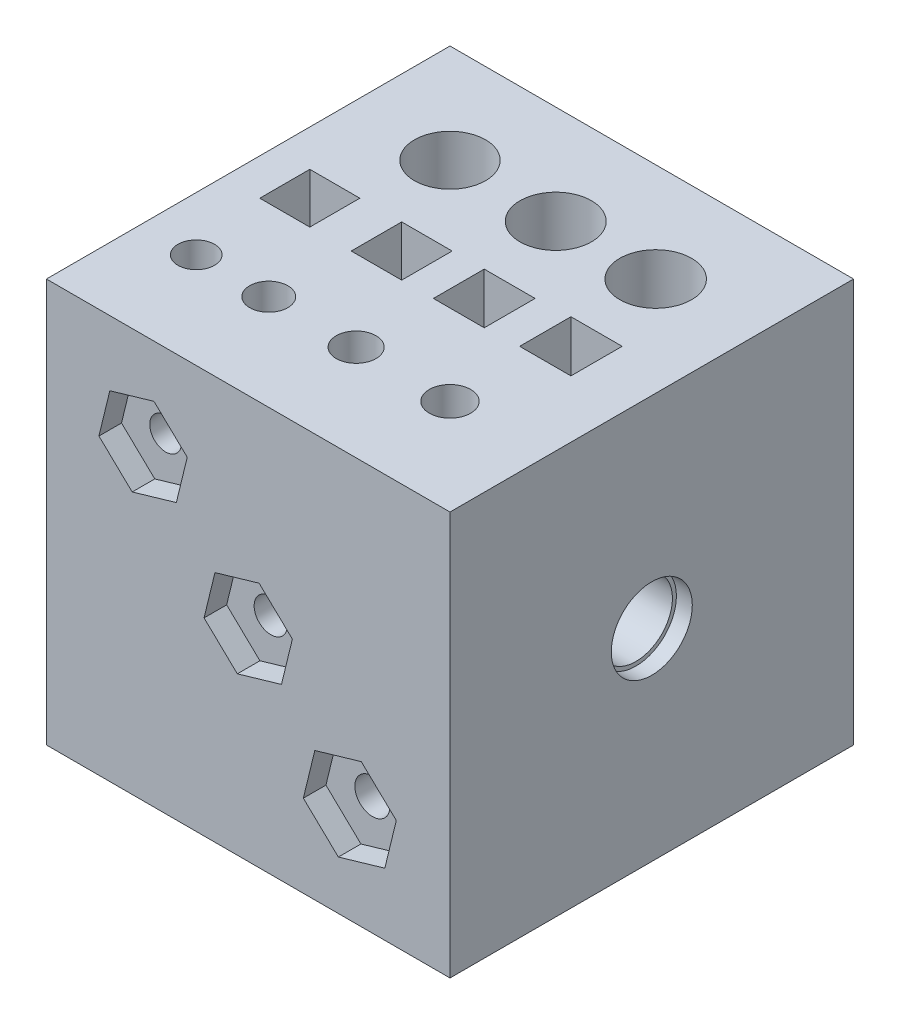
SolidWorks part; units mm, degrees
material "Copper"
ref_plane "Front Plane" through (0, 0, 0) normal (0, 0, 1) x (1, 0, 0)
ref_plane "Top Plane" through (0, 0, 0) normal (0, 1, 0) x (1, 0, 0)
ref_plane "Right Plane" through (0, 0, 0) normal (1, 0, 0) x (0, 0, -1)
sketch "Sketch1" plane through (0, 0, 0) normal (0, 1, 0) x (1, 0, 0)
  line L0 (-10.3903, 1.5671) -> (-7.2407, 1.5671)
  line L1 (-12.7, 12.7) -> (12.7, 12.7)
  line L2 (-12.7, 12.7) -> (-12.7, -12.7)
  line L3 (-12.7, -12.7) -> (12.7, -12.7)
  line L4 (12.7, 12.7) -> (12.7, -12.7)
  line L5 (5.8615, 1.7488) -> (9.0873, 1.7488)
  line L6 (5.8615, 1.7488) -> (5.8615, -1.477)
  line L7 (-4.6326, 1.5925) -> (-1.4576, 1.5925)
  line L8 (-4.6326, 1.5925) -> (-4.6326, -1.5825)
  line L9 (-4.6326, -1.5825) -> (-1.4576, -1.5825)
  line L10 (-1.4576, 1.5925) -> (-1.4576, -1.5825)
  line L11 (-4.6326, 1.5925) -> (-1.4576, -1.5825) construction
  line L12 (-4.6326, -1.5825) -> (-1.4576, 1.5925) construction
  line L13 (-10.3903, 1.5671) -> (-10.3903, -1.5825)
  line L14 (-10.3903, -1.5825) -> (-7.2407, -1.5825)
  line L15 (-7.2407, 1.5671) -> (-7.2407, -1.5825)
  line L16 (0.5377, 1.6179) -> (3.7381, 1.6179)
  line L17 (0.5377, 1.6179) -> (0.5377, -1.5825)
  line L18 (0.5377, -1.5825) -> (3.7381, -1.5825)
  line L19 (3.7381, 1.6179) -> (3.7381, -1.5825)
  line L20 (5.8615, -1.477) -> (9.0873, -1.477)
  line L21 (9.0873, 1.7488) -> (9.0873, -1.477)
  line L22 (0, -12.1469) -> (-0.4838, -11.2382)
  line L23 (-0.4838, -11.2382) -> (0.7604, -11.2382)
  line L24 (0.7604, -11.2382) -> (0, -12.1469)
  circle A0 centre (6.473, 6.473) radius 2.2606
  circle A1 centre (-6.473, 6.473) radius 2.2352
  circle A4 centre (6.6683, -6.6683) radius 1.3
  circle A5 centre (-9.3051, -6.6683) radius 1.15
  circle A6 centre (-4.7393, -6.6683) radius 1.2
  circle A7 centre (0.1814, 6.473) radius 2.2479
  circle A8 centre (0.7604, -6.6683) radius 1.25
  point P0 (0, 0)
  point P6 (-3.0451, 0.005)
  dimension "D3" = 4.5212
  dimension "D4" = 2.6
  dimension "D5" = 2.3
  dimension "D6" = 2.4
  dimension "D7" = 2.5
  dimension "D11" = 4.4704
  dimension "D12" = 4.4958
  dimension "D1" = 25.4
  dimension "D2" = 3.175
  dimension "D8" = 3.1496
  dimension "D9" = 3.2004
  dimension "D10" = 3.2258
extrude "Boss-Extrude1" add sketch "Sketch1" along normal blind 25.4 contours L4 L1 L2 L3 A8 A7 A6 A5 A4 A1 A0 L7 L10 L9 L8 L0 L15 L14 L13 L16 L19 L18 L17 L5 L21 L20 L6 L23 L24 L22 | L22 L23 L24 region at (0.0636, 0, 0.3299)
sketch "Sketch2" plane through (0, 0, 12.7) normal (0, 0, 1) x (1, 0, 0)
  line L0 (-0.6859, 9.8868) -> (0.6859, 15.5132) construction
  line L1 (-2.0934, 14.7006) -> (2.0934, 10.6994) construction
  line L2 (-2.7792, 11.8874) -> (2.7792, 13.5126) construction
  line L3 (-2.0934, 14.7006) -> (0.6859, 15.5132)
  line L4 (0.6859, 15.5132) -> (2.7792, 13.5126)
  line L5 (2.7792, 13.5126) -> (2.0934, 10.6994)
  line L6 (2.0934, 10.6994) -> (-0.6859, 9.8868)
  line L7 (-0.6859, 9.8868) -> (-2.7792, 11.8874)
  line L8 (-2.7792, 11.8874) -> (-2.0934, 14.7006)
  line L9 (-7.3031, 16.4901) -> (-5.9313, 22.1165) construction
  line L10 (-8.7105, 21.3039) -> (-4.5238, 17.3027) construction
  line L11 (-9.3964, 18.4907) -> (-3.8379, 20.1159) construction
  line L12 (-8.7105, 21.3039) -> (-5.9313, 22.1165)
  line L13 (-5.9313, 22.1165) -> (-3.8379, 20.1159)
  line L14 (-3.8379, 20.1159) -> (-4.5238, 17.3027)
  line L15 (-4.5238, 17.3027) -> (-7.3031, 16.4901)
  line L16 (-7.3031, 16.4901) -> (-9.3964, 18.4907)
  line L17 (-9.3964, 18.4907) -> (-8.7105, 21.3039)
  line L18 (5.6728, 3.0799) -> (7.1167, 9.0024) construction
  line L19 (4.1912, 8.147) -> (8.5983, 3.9352) construction
  line L20 (3.4692, 5.1857) -> (9.3203, 6.8965) construction
  line L21 (4.1912, 8.147) -> (7.1167, 9.0024)
  line L22 (7.1167, 9.0024) -> (9.3203, 6.8965)
  line L23 (9.3203, 6.8965) -> (8.5983, 3.9352)
  line L24 (8.5983, 3.9352) -> (5.6728, 3.0799)
  line L25 (5.6728, 3.0799) -> (3.4692, 5.1857)
  line L26 (3.4692, 5.1857) -> (4.1912, 8.147)
  circle A0 centre (0, 12.7) radius 1.05
  circle A1 centre (0, 12.7) radius 2.8956 construction
  circle A2 centre (-6.6172, 19.3033) radius 1.0033
  circle A3 centre (-6.6172, 19.3033) radius 2.8956 construction
  circle A4 centre (6.3948, 6.0411) radius 1.1049
  circle A5 centre (6.3948, 6.0411) radius 3.048 construction
  dimension "D1" = 2.1
  dimension "D2" = 5.7912
  dimension "D5" = 2.0066
  dimension "D6" = 5.7912
  dimension "D9" = 2.2098
  dimension "D10" = 6.096
  dimension "D3" = 60
  dimension "D4" = 60
  dimension "D7" = 60
  dimension "D8" = 60
  dimension "D11" = 60
  dimension "D12" = 60
extrude "Cut-Extrude2" cut sketch "Sketch2" against normal through all contours A2 | A0 | A4 region at (0, 12.7, 12.7) region at (-6.6172, 19.3033, 12.7) region at (6.3948, 6.0411, 12.7)
extrude "Cut-Extrude3" cut sketch "Sketch2<3>" against normal blind 1.4224 contours L17 L16 L15 L14 L13 L12 A2 | L8 L7 L6 L5 L4 L3 A0 | L26 L25 L24 L23 L22 L21 A4 region at (-0.6815, 15.031, 12.7) region at (-7.2987, 21.6343, 12.7) region at (5.6773, 8.4948, 12.7)
sketch "Sketch2<3>" plane through (0, 0, 12.7) normal (0, 0, 1) x (1, 0, 0) same geometry as "Sketch2"
extrude "Cut-Extrude6" cut sketch "Sketch1<4>" along normal blind 1.4224 contours L24 L23 L22 region at (0.0922, 0, 11.5411)
sketch "Sketch1<4>" plane through (0, 0, 0) normal (0, 1, 0) x (1, 0, 0) same geometry as "Sketch1"
sketch "Sketch4" plane through (12.7, 0, 0) normal (1, 0, 0) x (0, 0, -1)
  circle A0 centre (0, 12.7) radius 5.56
  circle A1 centre (0, 12.7) radius 2.3
  circle A2 centre (0, 12.7) radius 2.55
  dimension "D1" = 11.12
  dimension "D2" = 4.6
  dimension "D3" = 5.1
extrude "Cut-Extrude7" cut sketch "Sketch4" against normal blind 8.8 contours A1 region at (12.7, 12.7, 0)
extrude "Cut-Extrude8" cut sketch "Sketch4<3>" against normal blind 1 contours A2 A1 region at (12.7, 12.7, 2.4779)
sketch "Sketch4<3>" plane through (12.7, 0, 0) normal (1, 0, 0) x (0, 0, -1) same geometry as "Sketch4"
